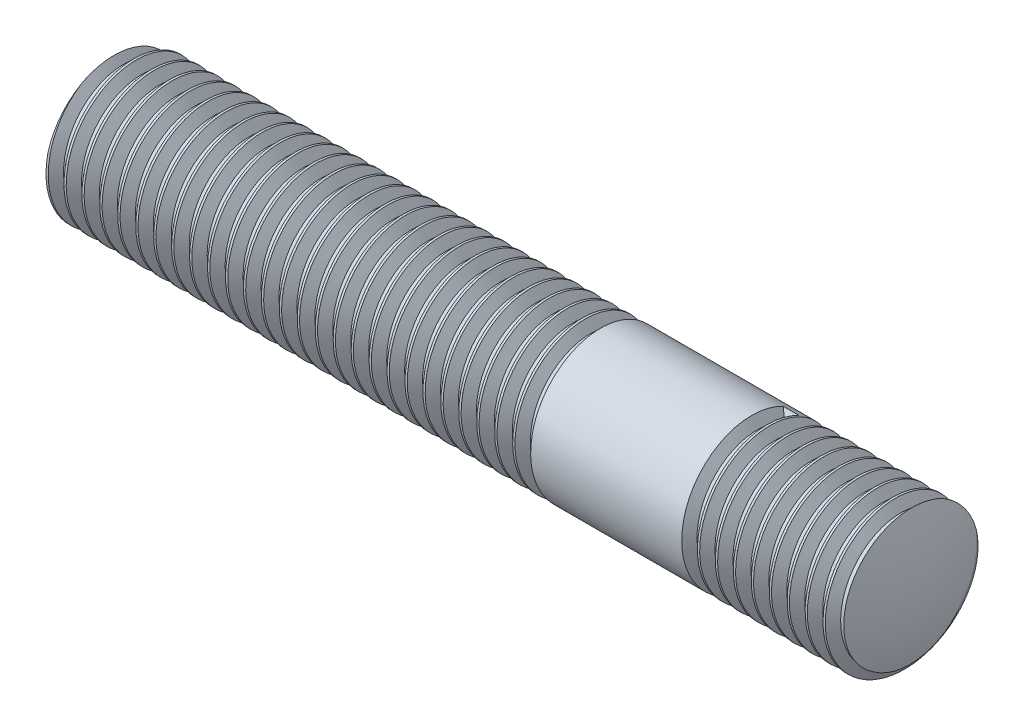
SolidWorks part; units mm, degrees
ref_plane "Front Plane" through (0, 0, 0) normal (0, 0, 1) x (1, 0, 0)
ref_plane "Top Plane" through (0, 0, 0) normal (0, 1, 0) x (1, 0, 0)
ref_plane "Right Plane" through (0, 0, 0) normal (1, 0, 0) x (0, 0, -1)
sketch "Sketch1" plane through (0, 0, 0) normal (0, 0, 1) x (1, 0, 0)
  line L0 (0, 0) -> (68, 0) construction
  line L1 (0, 0) -> (0, 45.3333) construction
  line L2 (68, 0) -> (68, 19.866) construction
  line L3 (1, 6) -> (67, 6)
  line L4 (0, 0) -> (68, 0)
  arc A0 (0, 0) -> (1, 6) centre (32.0282, -2.2547) cw
  arc A1 (67, 6) -> (68, 0) centre (49.5, 0) cw
  point P9 (65.8385, 12.8598)
  dimension "D1" = 68
  dimension "D2" = 1
  dimension "D3" = 1
  dimension "D4" = 12
revolve "Revolve1" add sketch "Sketch1" angle 360 about L4
thread "Thread1" pitch 1.5 method cut trim with start face yes trim with end face yes profile "Thread Profile1" start angle 0, offset 5, length 45, pitch 1.5, diameter 12
ref_plane "Plane1" through (-4, 0, -6) normal (0, -1, 0) x (0, 0, -1)
sketch "Thread Profile1" plane through (-4, 0, -6) normal (0, -1, 0) x (0, 0, -1)
  line L0 (0, 0) -> (0, 1.5) construction
  line L11 (0, 0) -> (0, 1.3125)
  line L12 (0, 1.3125) -> (-0.8119, 0.8437)
  line L13 (-0.8119, 0.8437) -> (-0.8119, 0.4687)
  line L15 (-0.8119, 0.4687) -> (0, 0)
  line L17 (-0.8119, 0.6562) -> (0, 0.6562) construction
  point P2 (0, 0)
  dimension "Pitch" = 1.5
  dimension "Profile_Angle" = 60
  dimension "Profile_Land" = 0.375
  dimension "Profile_Height" = 0.8119
thread "Thread2" pitch 1.5 method cut trim with start face yes trim with end face yes profile "Thread Profile2" start angle 0, offset 5, length 17, pitch 1.5, diameter 12
ref_plane "Plane2" through (72, 0, 6) normal (0, -1, 0) x (0, 0, 1)
sketch "Thread Profile2" plane through (72, 0, 6) normal (0, -1, 0) x (0, 0, 1)
  line L0 (0, 0) -> (0, 1.5) construction
  line L11 (0, 0) -> (0, 1.3125)
  line L12 (0, 1.3125) -> (-0.8119, 0.8437)
  line L13 (-0.8119, 0.8437) -> (-0.8119, 0.4687)
  line L15 (-0.8119, 0.4687) -> (0, 0)
  line L17 (-0.8119, 0.6562) -> (0, 0.6562) construction
  point P2 (0, 0)
  dimension "Pitch" = 1.5
  dimension "Profile_Angle" = 60
  dimension "Profile_Land" = 0.375
  dimension "Profile_Height" = 0.8119
